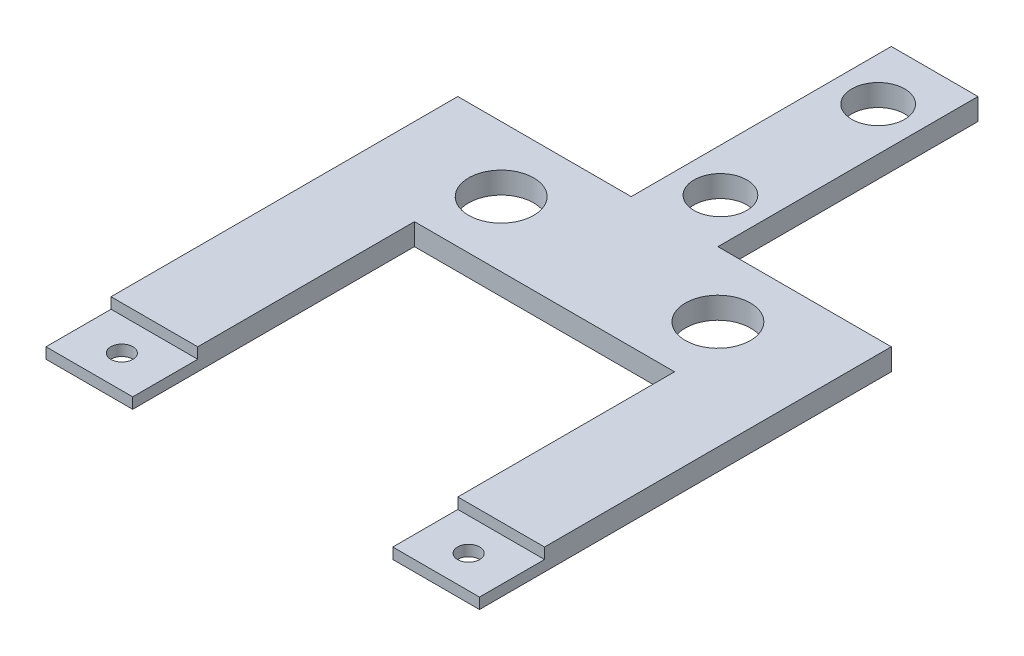
SolidWorks part; units mm, degrees
ref_plane "Front Plane" through (0, 0, 0) normal (0, 0, 1) x (1, 0, 0)
ref_plane "Top Plane" through (0, 0, 0) normal (0, 1, 0) x (1, 0, 0)
ref_plane "Right Plane" through (0, 0, 0) normal (1, 0, 0) x (0, 0, -1)
sketch "Sketch1" plane through (0, 0, 0) normal (0, 1, 0) x (1, 0, 0)
  line L1 (-15.875, 15.0812) -> (15.875, 15.0812)
  line L2 (-15.875, 15.0812) -> (-15.875, -15.0812)
  line L3 (-15.875, -15.0812) -> (15.875, -15.0812)
  line L4 (15.875, 15.0812) -> (15.875, -15.0812)
  line L5 (-9.525, -15.0812) -> (9.525, -15.0812)
  line L6 (-9.525, -15.0812) -> (-9.525, 5.5562)
  line L7 (-9.525, 5.5562) -> (9.525, 5.5562)
  line L8 (9.525, -15.0812) -> (9.525, 5.5562)
  line L9 (-3.175, 15.0813) -> (3.175, 15.0813)
  line L10 (-3.175, 15.0813) -> (-3.175, 34.1313)
  line L11 (-3.175, 34.1313) -> (3.175, 34.1313)
  line L12 (3.175, 15.0813) -> (3.175, 34.1313)
  point P4 (0, 15.0813)
  point P6 (-15.875, 0)
  point P11 (0, 5.5563)
  point P16 (0, 15.0813)
  dimension "D1" = 31.75
  dimension "D2" = 30.1625
  dimension "D3" = 6.35
  dimension "D4" = 9.525
  dimension "D5" = 6.35
  dimension "D6" = 19.05
extrude "Boss-Extrude1" add sketch "Sketch1" along normal mid plane 1.5875 contours L8 L3 L4 L1 L2 L6 L7 | L10 L9 L12 L11 region at (-9.525, 0, -14.6433)
sketch "Sketch2" plane through (0, 0.7937, 0) normal (0, 1, 0) x (1, 0, 0)
  line L0 (-9.525, -15.0812) -> (-9.525, 5.5562) construction
  line L1 (-15.875, -15.0812) -> (-9.525, -15.0812)
  line L2 (-15.875, -15.0812) -> (-15.875, -10.3187)
  line L3 (-15.875, -10.3187) -> (-9.525, -10.3187)
  line L4 (-9.525, -15.0812) -> (-9.525, -10.3187)
  line L5 (15.875, 15.0812) -> (15.875, -15.0812) construction
  line L6 (9.525, -15.0812) -> (15.875, -15.0812)
  line L7 (9.525, -15.0812) -> (9.525, -10.3187)
  line L8 (9.525, -10.3187) -> (15.875, -10.3187)
  line L9 (15.875, -15.0812) -> (15.875, -10.3187)
  dimension "D1" = 4.7625
extrude "Cut-Extrude1" cut sketch "Sketch2" against normal blind 0.7937
sketch "Sketch3" plane through (0, 0.7937, 0) normal (0, 1, 0) x (1, 0, 0)
  line L0 (-9.525, -10.3187) -> (-15.875, -10.3187) construction
  line L1 (-15.875, -10.3187) -> (-15.875, -15.0812) construction
  line L2 (0, -1000) -> (0, 49000) construction
  line L4 (-15.875, 15.0812) -> (-3.175, 15.0812) construction
  line L5 (-3.175, 34.1313) -> (3.175, 34.1313) construction
  circle A0 centre (-12.7, -12.7) radius 0.8065
  circle A1 centre (-7.9375, 10.3187) radius 2.3813
  circle A2 centre (12.7, -12.7) radius 0.8065
  circle A3 centre (7.9375, 10.3187) radius 2.3813
  circle A4 centre (0, 18.442) radius 1.9364
  circle A5 centre (0, 29.994) radius 1.9364
  point P6 (-12.7, -10.3187)
  point P9 (-15.875, -12.7)
  dimension "D1" = 1.6129
  dimension "D2" = 4.7625
  dimension "D3" = 7.9375
  dimension "D4" = 4.7625
  dimension "D5" = 11.552
  dimension "D6" = 4.1372
  dimension "D7" = 3.8728
extrude "Cut-Extrude2" cut sketch "Sketch3" against normal up to surface (1.5875 mm away) from surface up to face at (0, -0.7937, -6.6146) starting at face at (0, 0.7937, -8.2021)
